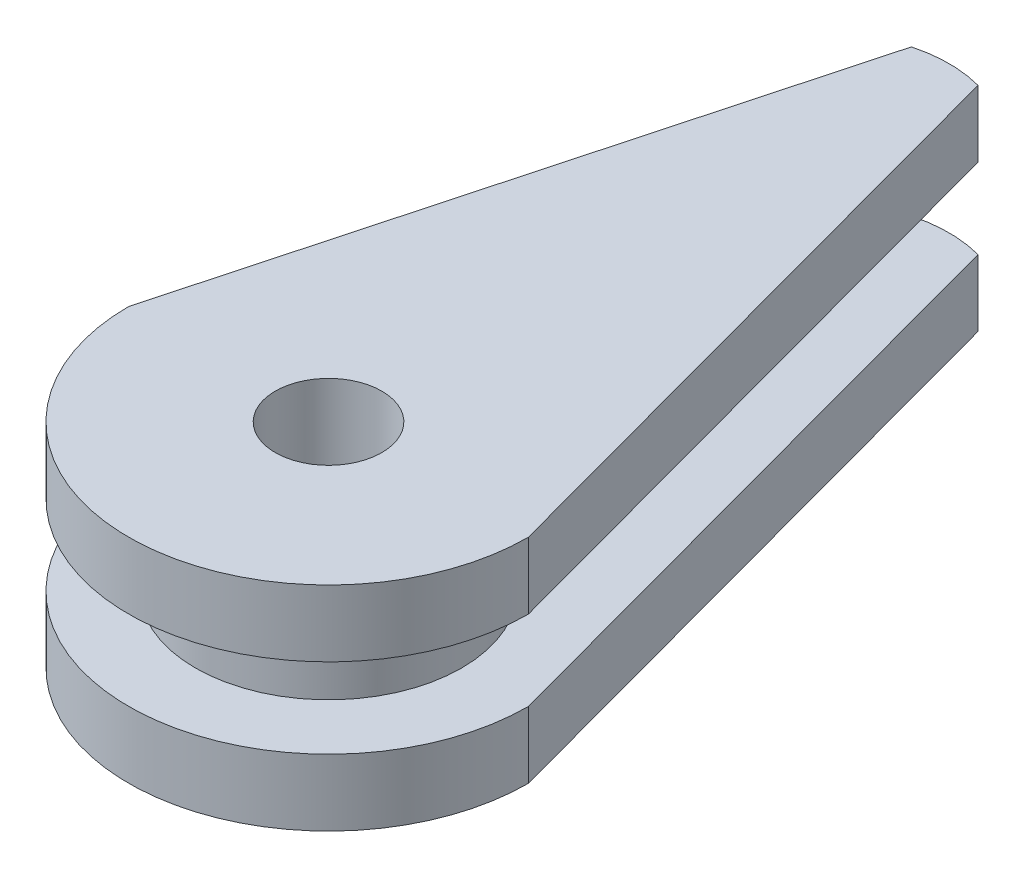
SolidWorks part; units mm, degrees
ref_plane "前视基准面" through (0, 0, 0) normal (0, 0, 1) x (1, 0, 0)
ref_plane "上视基准面" through (0, 0, 0) normal (0, 1, 0) x (1, 0, 0)
ref_plane "右视基准面" through (0, 0, 0) normal (1, 0, 0) x (0, 0, -1)
sketch "草图1" plane through (0, 0, 0) normal (0, 1, 0) x (1, 0, 0)
  circle A0 centre (0, 0) radius 5
extrude "凸台-拉伸1" add sketch "草图1" along normal blind 3
sketch "草图2" plane through (0, 3, 0) normal (0, 1, 0) x (1, 0, 0)
  line L0 (0, 5) -> (0, -5)
  circle A0 centre (0, 0) radius 5 construction
ref_plane "基准面1" through (0, 0, 5) normal (0, 0, 1) x (1, 0, 0)
sketch "草图3" plane through (0, 0, 5) normal (0, 0, 1) x (1, 0, 0)
  line L0 (-5, 1.5) -> (5, 1.5)
  line L1 (-5, 3) -> (-5, 0) construction
  line L2 (5, 0) -> (5, 3) construction
ref_plane "基准面2" through (0, 1.5, 0) normal (0, 1, 0) x (1, 0, 0)
sketch "草图4" plane through (0, 1.5, 0) normal (0, 1, 0) x (1, 0, 0)
  circle A0 centre (0, 0) radius 5
sketch "草图6" plane through (0, 0, 0) normal (0, -1, 0) x (1, 0, 0)
  line L0 (0, 5) -> (0, -18.5)
  line L1 (0, -18.5) -> (5, 0)
  line L2 (0, -18.5) -> (-5, 0)
  circle A0 centre (0, 0) radius 5 construction
  arc A1 (-5, 0) -> (5, 0) centre (0, 0) cw
  circle M1 centre (0, 0) radius 5
extrude "凸台-拉伸3" add sketch "草图6" along normal blind 2.5 contours L2 L0 M1 | L2 L0 M1 | L0 L1 M1 | L1 L0 M1 region at (2.1019, 0, 0.0099) region at (-2.1019, 0, 0.0099) region at (1.3688, 0, -9.0621) region at (-1.3688, 0, -9.0621)
mirror "镜向1" about plane through (0, 1.5, 0) normal (0, 1, 0) of "凸台-拉伸3"
sketch "草图8" plane through (0, 5.5, 0) normal (0, 1, 0) x (1, 0, 0)
  line L0 (0, 0) -> (0, -2.5)
  line L1 (0, 5) -> (0, -5) construction
  line L2 (0, 18.5) -> (-2.6426, 28.2778)
  line L3 (0, 18.5) -> (2.6426, 28.2778)
  line L4 (-7.5, 0) -> (-1.25, 23.125)
  line L6 (0, 18.5) -> (-5, 0) construction
  line L8 (1.25, 23.125) -> (7.5, 0)
  arc A0 (-5, 0) -> (5, 0) centre (0, 0) ccw
  circle A1 centre (0, 0) radius 5 construction
  arc A2 (-7.5, 0) -> (7.5, 0) centre (0, 0) ccw
  arc A3 (-1.25, 23.125) -> (1.25, 23.125) centre (0, 18.5) cw
  line M4 (0, 18.5) -> (-5, 0)
  arc M5 (-5, 0) -> (5, 0) centre (0, 0) ccw
  line M6 (5, 0) -> (0, 18.5)
extrude "凸台-拉伸4" add sketch "草图8" against normal up to surface (2.5 mm away) contours L4 A2 L8 L3 L2 M6 M5 M4 | A3 L2 L3 region at (0.9542, 5.5, -20.7235) region at (0, 5.5, -21.657)
extrude "凸台-拉伸5" add sketch "草图8<4>" along normal up to surface (-5.5 mm away) from surface contours L4 A2 L8 L3 L2 M6 M5 M4 | A3 L2 L3 region at (0.9542, 5.5, -20.7235) region at (0, 5.5, -21.657) region at (0, 5.5, -3.6965) up to face at (0, 0, -8.6729) starting at face at (0, -2.5, -4.5)
sketch "草图8<4>" plane through (0, 5.5, 0) normal (0, 1, 0) x (1, 0, 0) same geometry as "草图8"
sketch "草图9" plane through (0, -2.5, 0) normal (0, -1, 0) x (1, 0, 0)
  circle A0 centre (0, 0) radius 2
extrude "切除-拉伸1" cut sketch "草图9" against normal through all
